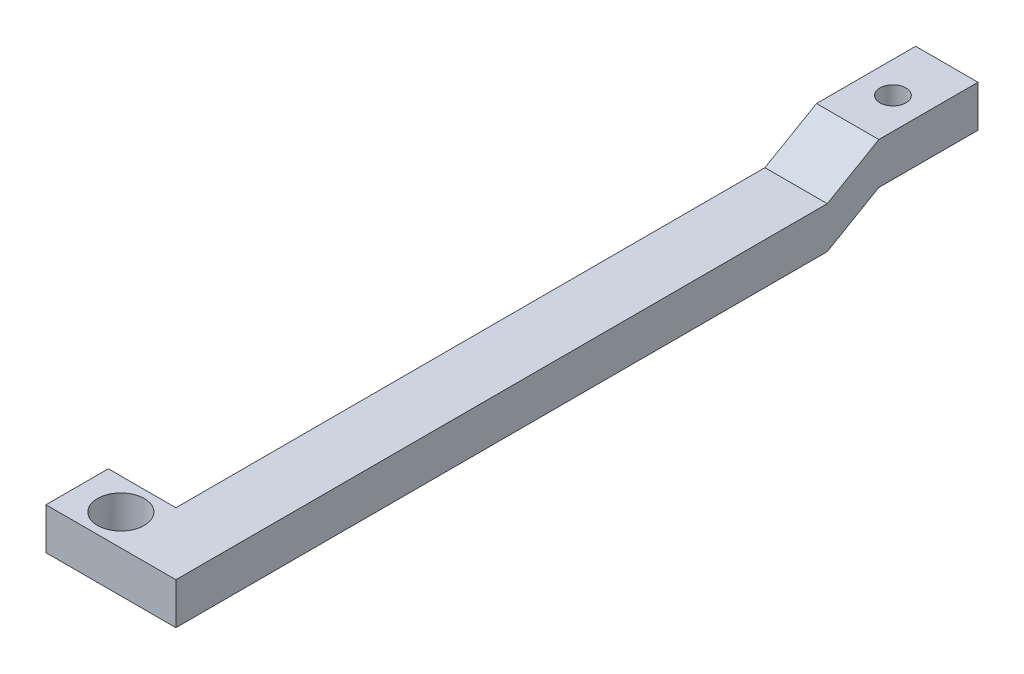
SolidWorks part; units mm, degrees
material "Copper"
ref_plane "Front Plane" through (0, 0, 0) normal (0, 0, 1) x (1, 0, 0)
ref_plane "Top Plane" through (0, 0, 0) normal (0, 1, 0) x (1, 0, 0)
ref_plane "Right Plane" through (0, 0, 0) normal (1, 0, 0) x (0, 0, -1)
sketch "Sketch1" plane through (0, 0, 0) normal (1, 0, 0) x (0, 0, -1)
  line L0 (12, 8) -> (12, 0)
  line L2 (0, 0) -> (125.3795, 0)
  line L3 (0, 0) -> (0, 8)
  line L4 (0, 8) -> (125.3795, 8)
  line L7 (154.39, 13.73) -> (135.3041, 13.73)
  line L8 (135.3041, 13.73) -> (125.3795, 8)
  line L9 (154.39, 13.73) -> (154.39, 5.73)
  line L10 (135.3041, 5.73) -> (125.3795, 0)
  line L11 (135.3041, 5.73) -> (154.39, 5.73)
  dimension "D2" = 8
  dimension "D3" = 12
  dimension "D4" = 150
  dimension "D5" = 150
extrude "Boss-Extrude1" add sketch "Sketch1" against normal blind 12 contours L2 L10 L11 L9 L7 L8 L4 L3
extrude "Boss-Extrude2" add sketch "Sketch1<3>" against normal blind 25 contours L4 L3 L2 L0 region at (0, 4, -6)
sketch "Sketch1<3>" plane through (0, 0, 0) normal (1, 0, 0) x (0, 0, -1) same geometry as "Sketch1"
sketch "Sketch2" plane through (0, 8, 0) normal (0, 1, 0) x (1, 0, 0)
  line L3 (-25, 6) -> (0, 6) construction
  line L4 (-25, 0) -> (-25, 12) construction
  line L5 (0, -107.0669) -> (0, 107.0669) construction
  circle A1 centre (-16.59, 6) radius 4.5
  dimension "D2" = 16.59
extrude "Cut-Extrude1" cut sketch "Sketch2" along direction (0, -1, 0) on the side against the normal up to next (8 mm away) contours A1
sketch "Sketch4" plane through (0, 13.73, 0) normal (0, 1, 0) x (1, 0, 0)
  line L0 (-6, 154.39) -> (-6, 135.3041) construction
  line L1 (-12, 154.39) -> (0, 154.39) construction
  line L2 (-12, 135.3041) -> (0, 135.3041) construction
  circle A0 centre (-6, 144.02) radius 2.5
  dimension "D1" = 10.37
extrude "Cut-Extrude2" cut sketch "Sketch4" along direction (0, -1, 0) on the side against the normal up to next (8 mm away)
